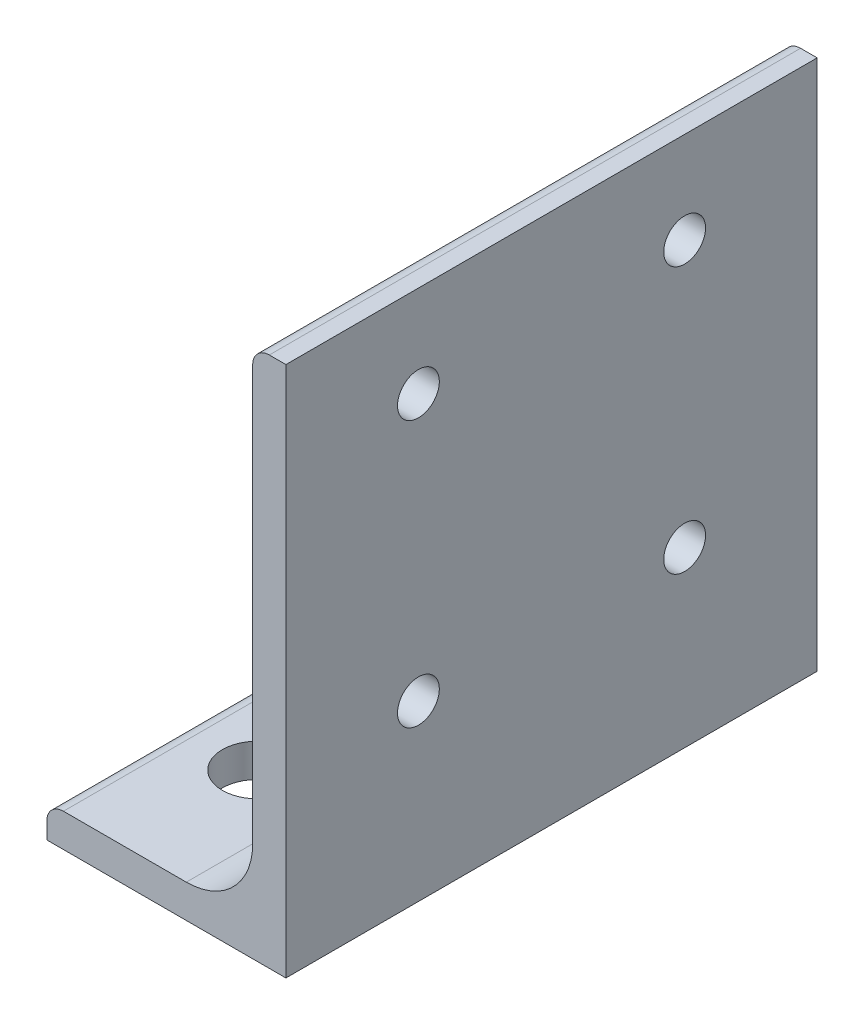
SolidWorks part; units mm, degrees
ref_plane "Front Plane" through (0, 0, 0) normal (0, 0, 1) x (1, 0, 0)
ref_plane "Top Plane" through (0, 0, 0) normal (0, 1, 0) x (1, 0, 0)
ref_plane "Right Plane" through (0, 0, 0) normal (1, 0, 0) x (0, 0, -1)
sketch "Sketch2" plane through (0, 0, 0) normal (0, 0, 1) x (1, 0, 0)
  line L0 (-25.4, 0) -> (25.4, 0)
  line L1 (25.4, 0) -> (25.4, 50.8)
  line L2 (25.4, 50.8) -> (22.225, 50.8) construction
  line L3 (22.225, 49.2125) -> (22.225, 9.525)
  line L4 (15.875, 3.175) -> (-23.8125, 3.175)
  line L5 (-25.4, 0) -> (-25.4, 3.175) construction
  line L6 (23.8125, 50.8) -> (25.4, 50.8)
  line L7 (-25.4, 1.5875) -> (-25.4, 0)
  arc A0 (22.225, 49.2125) -> (23.8125, 50.8) centre (23.8125, 49.2125) cw
  arc A1 (-25.4, 1.5875) -> (-23.8125, 3.175) centre (-23.8125, 1.5875) cw
  arc A2 (22.225, 9.525) -> (15.875, 3.175) centre (15.875, 9.525) cw
  dimension "Inside Radius" = 6.35
  dimension "Vert" = 50.8
  dimension "Horz" = 50.8
  dimension "Thickness" = 3.175
extrude "Boss-Extrude1" add sketch "Sketch2" along normal mid plane 50.8
sketch "Break Locations" plane through (0, 0, 0) normal (1, 0, 0) x (0, 0, -1)
  line L1 (-25.4, 0) -> (-25.4, 50.8) construction
  line L2 (25.4, 0) -> (25.4, 50.8) construction
  point P0 (17.78, 0)
  point P1 (-17.78, 0)
  dimension "D1" = 43.18
  dimension "D2" = 43.18
ref_plane "Contact Plane 1" through (0, 3.175, 0) normal (0, 1, 0) x (1, 0, 0)
ref_plane "Contact Plane 2" through (22.225, 0, 0) normal (-1, 0, 0) x (0, 0, 1)
sketch "Sketch3" plane through (0, 0, -25.4) normal (0, 0, -1) x (-1, 0, 0)
  line L0 (25.4, 1.5875) -> (25.4, 0) construction
  line L1 (-2.54, 8.3996) -> (25.4, 8.3996)
  line L2 (-2.54, 8.3996) -> (-2.54, -5.4313)
  line L3 (-2.54, -5.4313) -> (25.4, -5.4313)
  line L4 (25.4, 8.3996) -> (25.4, -5.4313)
  line L5 (-25.4, 0) -> (-25.4, 50.8) construction
  point P6 (25.4, 0.7937)
  dimension "D1" = 22.86
extrude "Cut-Extrude1" cut sketch "Sketch3" against normal through all
fillet "Fillet1" radius 1.5875 1 edges at (2.54, 3.175, 0)
sketch "Sketch4" plane through (0, 3.175, 0) normal (0, 1, 0) x (1, 0, 0)
  line L0 (10.0013, 25.4) -> (10.0013, -25.4) construction
  line L1 (15.875, 25.4) -> (4.1275, 25.4) construction
  line L2 (15.875, -25.4) -> (4.1275, -25.4) construction
  circle A0 centre (10.0013, 12.7) radius 3.3782
  circle A1 centre (10.0013, -12.7) radius 3.3782
  dimension "D1" = 6.7564
  dimension "D2" = 25.4
  dimension "D3" = 12.7
extrude "Cut-Extrude2" cut sketch "Sketch4" against normal through all
sketch "Sketch5" plane through (25.4, 0, 0) normal (1, 0, 0) x (0, 0, -1)
  line L0 (-25.4, 0) -> (25.4, 0) construction
  line L1 (25.4, 0) -> (25.4, 50.8) construction
  line L2 (0, 50.8) -> (0, 0) construction
  line L3 (-25.4, 50.8) -> (25.4, 50.8) construction
  line L4 (-25.4, 25.4) -> (25.4, 25.4) construction
  line L5 (-25.4, 0) -> (-25.4, 50.8) construction
  line L6 (0, 29.3279) -> (12.7279, 42.0558) construction
  line L7 (0, 29.3279) -> (12.7279, 16.6) construction
  circle A0 centre (12.7279, 16.6) radius 2
  circle A1 centre (-12.7279, 16.6) radius 2
  circle A2 centre (-12.7279, 42.0558) radius 2
  circle A3 centre (12.7279, 42.0558) radius 2
  circle A4 centre (0, 29.3279) radius 18 construction
  point P16 (0, 0)
  point P17 (0, 28.3043)
  point P20 (25.4, 25.4)
  point P21 (0, 0)
  dimension "D1" = 4
  dimension "D3" = 36
  dimension "D2" = 45
  dimension "D4" = 45
  dimension "D5" = 16.6
extrude "Cut-Extrude3" cut sketch "Sketch5" against normal through all
equation "\"D1@Break Locations\"=.85*\"Vert@Sketch2\""
equation "\"D2@Break Locations\"=\"D1@Break Locations\""
